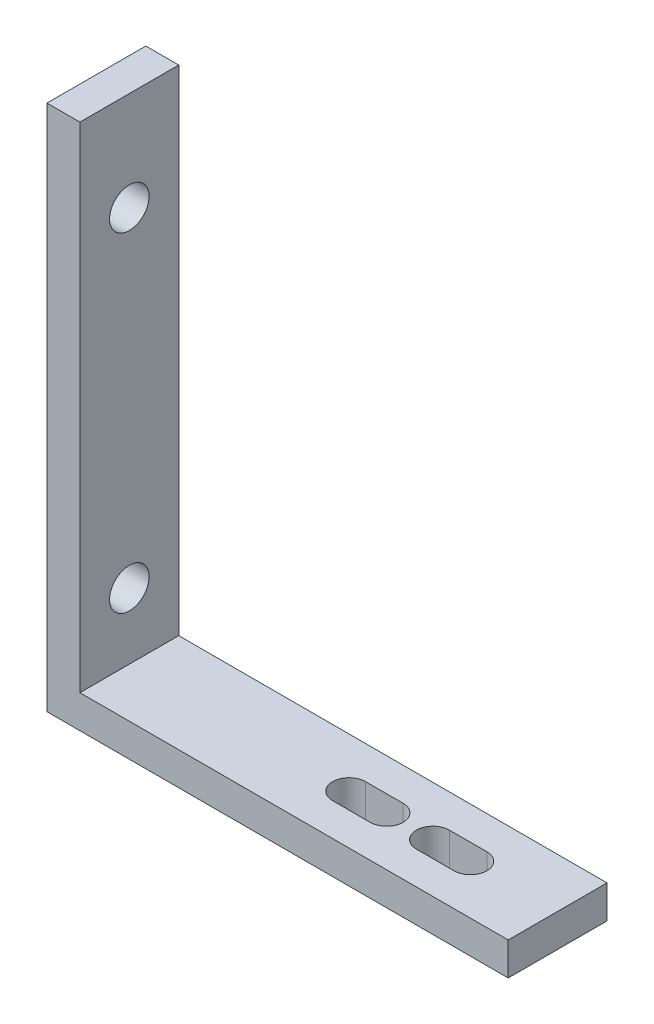
SolidWorks part; units mm, degrees
ref_plane "Front Plane" through (0, 0, 0) normal (0, 0, 1) x (1, 0, 0)
ref_plane "Top Plane" through (0, 0, 0) normal (0, 1, 0) x (1, 0, 0)
ref_plane "Right Plane" through (0, 0, 0) normal (1, 0, 0) x (0, 0, -1)
sketch "Sketch1" plane through (0, 0, 0) normal (0, 1, 0) x (1, 0, 0)
  line L1 (0, 0) -> (70, 0)
  line L2 (0, 0) -> (0, 15)
  line L3 (0, 15) -> (70, 15)
  line L4 (70, 0) -> (70, 15)
  dimension "D1" = 15
  dimension "D2" = 70
extrude "Boss-Extrude1" add sketch "Sketch1" along normal blind 5
sketch "Sketch2" plane through (0, 5, 0) normal (0, 1, 0) x (1, 0, 0)
  line L0 (0, 15) -> (5, 15)
  line L1 (70, 15) -> (0, 15) construction
  line L2 (0, 0) -> (5, 0)
  line L3 (0, 0) -> (70, 0) construction
  line L4 (5, 15) -> (5, 0)
  line L5 (0, 15) -> (0, 0)
extrude "Boss-Extrude2" add sketch "Sketch2" along normal blind 75
sketch "Sketch3" plane through (0, 0, 0) normal (0, -1, 0) x (-1, 0, 0)
  line L0 (0, 7.5) -> (-70, 7.5)
  line L1 (0, 15) -> (0, 0) construction
  line L2 (-70, 0) -> (-70, 15) construction
sketch "Sketch4" plane through (0, 0, 0) normal (-1, 0, 0) x (0, 0, 1)
  line L0 (-7.5, 80) -> (-7.5, 0)
  line L1 (-15, 80) -> (0, 80) construction
  line L2 (-15, 0) -> (0, 0) construction
  line L3 (-7.5, 0) -> (-7.5, 15)
  line L4 (-7.5, 80) -> (-7.5, 65)
hole_wizard "Ø6.0mm Dowel Hole1" positions "Sketch5" profile "Sketch6" hole size "Ø6.0" standard "ANSI Metric" end condition up to next
sketch "Sketch5" plane through (0, 0, 0) normal (-1, 0, 0) x (0, 0, 1)
  point P0 (-7.5, 65)
  point P3 (-7.5, 15)
sketch "Sketch6" plane through (0, 65, -7.5) normal (0, 1, 0) x (0, 0, 1)
  line L0 (0, 0) -> (0, 5)
  line L1 (0, 5) -> (3, 5)
  line L2 (3, 5) -> (3, 0)
  line L5 (3, 0) -> (0, 0)
  line L11 (0, -6.35) -> (0, 107.95) construction
  dimension "Thru Hole Dia." = 6
  dimension "Thru Hole Depth" = 5
hole_wizard "Ø6.0mm Dowel Slot1" positions "Sketch9" profile "Sketch8" size "Ø5.0" standard "ANSI Metric" slot yes end condition up to next
sketch "Sketch9" plane through (0, 0, 0) normal (0, -1, 0) x (-1, 0, 0)
  line L0 (-35.864, 7.4848) -> (-46.564, 7.4848) construction
  point P0 (-41.214, 7.4848)
  point P5 (-53.9443, 7.4749)
  dimension "D1" = 10.7
sketch "Sketch8" plane through (41.214, 0, -7.4848) normal (1, 0, 0) x (0, 0, -1)
  line L0 (0, 0) -> (0, 5)
  line L1 (0, 5) -> (2.5, 5)
  line L2 (2.5, 5) -> (2.5, 0)
  line L5 (2.5, 0) -> (0, 0)
  line L11 (0, -6.35) -> (0, 107.95) construction
  dimension "Thru Hole Dia." = 5
  dimension "Thru Hole Depth" = 5
